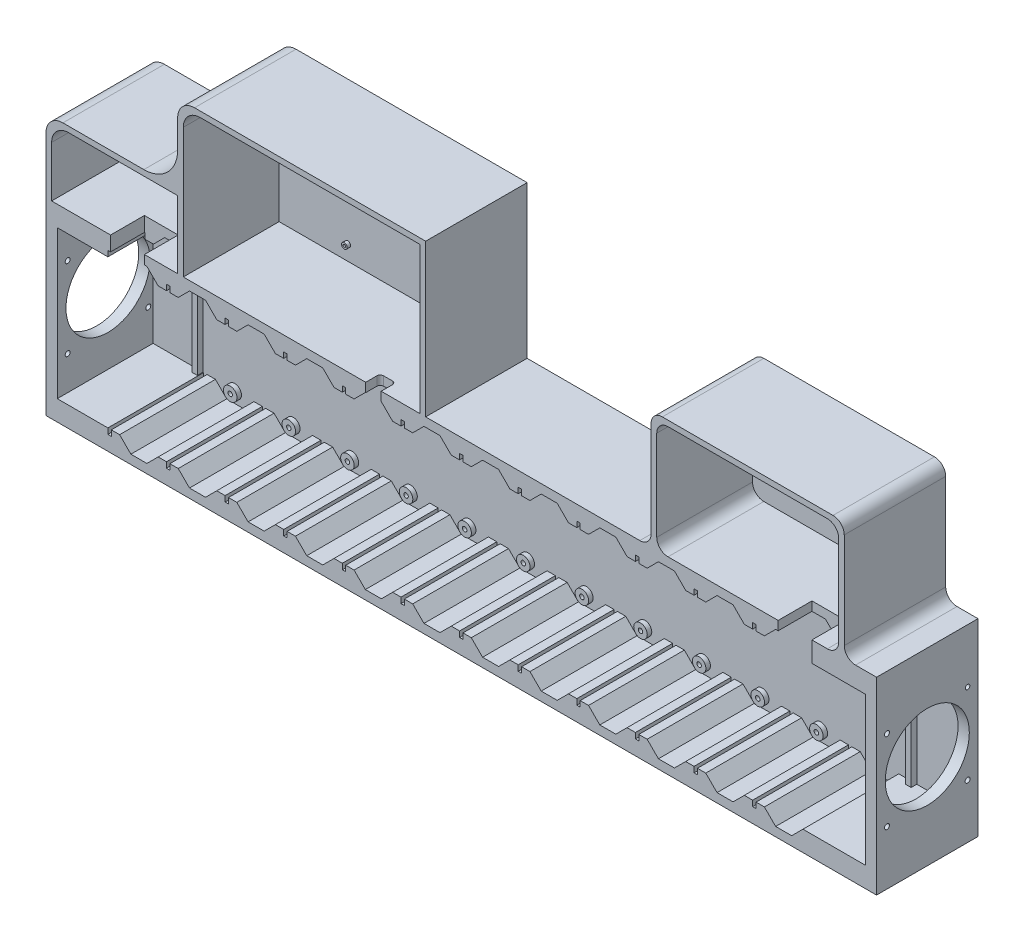
SolidWorks part; units mm, degrees
ref_plane "Front Plane" through (0, 0, 0) normal (0, 0, 1) x (1, 0, 0)
ref_plane "Top Plane" through (0, 0, 0) normal (0, 1, 0) x (1, 0, 0)
ref_plane "Right Plane" through (0, 0, 0) normal (1, 0, 0) x (0, 0, -1)
sketch "Szkic1" plane through (0, 0, 0) normal (0, 0, 1) x (1, 0, 0)
  line L0 (-48.95, 65) -> (-38.65, 65)
  line L1 (-38.65, 65) -> (-28.65, 75)
  line L2 (-28.65, 75) -> (-14.45, 75)
  line L3 (-14.45, 75) -> (-4.45, 65)
  line L4 (-4.45, 65) -> (13.35, 65)
  line L5 (13.35, 65) -> (23.35, 75)
  line L6 (23.35, 75) -> (37.55, 75)
  line L7 (37.55, 75) -> (47.55, 65)
  line L8 (-48.95, -66.4) -> (-38.65, -66.4)
  line L9 (-38.65, -66.4) -> (-28.65, -76.4)
  line L10 (-28.65, -76.4) -> (-14.45, -76.4)
  line L11 (-14.45, -76.4) -> (-4.45, -66.4)
  line L12 (-4.45, -66.4) -> (13.35, -66.4)
  line L13 (13.35, -66.4) -> (23.35, -76.4)
  line L14 (23.35, -76.4) -> (37.55, -76.4)
  line L15 (37.55, -76.4) -> (47.55, -66.4)
  line L16 (47.55, 65) -> (65.35, 65)
  line L17 (47.55, -66.4) -> (65.35, -66.4)
  line L18 (65.35, 65) -> (75.35, 75)
  line L19 (75.35, 75) -> (89.55, 75)
  line L20 (89.55, 75) -> (99.55, 65)
  line L21 (99.55, 65) -> (117.35, 65)
  line L22 (117.35, 65) -> (127.35, 75)
  line L23 (127.35, 75) -> (141.55, 75)
  line L24 (141.55, 75) -> (151.55, 65)
  line L25 (65.35, -66.4) -> (75.35, -76.4)
  line L26 (75.35, -76.4) -> (89.55, -76.4)
  line L27 (89.55, -76.4) -> (99.55, -66.4)
  line L28 (99.55, -66.4) -> (117.35, -66.4)
  line L29 (117.35, -66.4) -> (127.35, -76.4)
  line L30 (127.35, -76.4) -> (141.55, -76.4)
  line L31 (141.55, -76.4) -> (151.55, -66.4)
  line L32 (151.55, 65) -> (169.35, 65)
  line L33 (151.55, -66.4) -> (169.35, -66.4)
  line L34 (169.35, 65) -> (179.35, 75)
  line L35 (179.35, 75) -> (193.55, 75)
  line L36 (193.55, 75) -> (203.55, 65)
  line L37 (203.55, 65) -> (221.35, 65)
  line L38 (221.35, 65) -> (231.35, 75)
  line L39 (231.35, 75) -> (245.55, 75)
  line L40 (245.55, 75) -> (255.55, 65)
  line L41 (169.35, -66.4) -> (179.35, -76.4)
  line L42 (179.35, -76.4) -> (193.55, -76.4)
  line L43 (193.55, -76.4) -> (203.55, -66.4)
  line L44 (203.55, -66.4) -> (221.35, -66.4)
  line L45 (221.35, -66.4) -> (231.35, -76.4)
  line L46 (231.35, -76.4) -> (245.55, -76.4)
  line L47 (245.55, -76.4) -> (255.55, -66.4)
  line L48 (255.55, 65) -> (273.35, 65)
  line L49 (255.55, -66.4) -> (273.35, -66.4)
  line L50 (273.35, 65) -> (283.35, 75)
  line L51 (283.35, 75) -> (297.55, 75)
  line L52 (297.55, 75) -> (307.55, 65)
  line L53 (307.55, 65) -> (325.35, 65)
  line L54 (325.35, 65) -> (335.35, 75)
  line L55 (335.35, 75) -> (349.55, 75)
  line L56 (349.55, 75) -> (359.55, 65)
  line L57 (273.35, -66.4) -> (283.35, -76.4)
  line L58 (283.35, -76.4) -> (297.55, -76.4)
  line L59 (297.55, -76.4) -> (307.55, -66.4)
  line L60 (307.55, -66.4) -> (325.35, -66.4)
  line L61 (325.35, -66.4) -> (335.35, -76.4)
  line L62 (335.35, -76.4) -> (349.55, -76.4)
  line L63 (349.55, -76.4) -> (359.55, -66.4)
  line L64 (359.55, 65) -> (377.35, 65)
  line L65 (359.55, -66.4) -> (377.35, -66.4)
  line L66 (377.35, 65) -> (387.35, 75)
  line L67 (387.35, 75) -> (401.55, 75)
  line L68 (401.55, 75) -> (411.55, 65)
  line L69 (411.55, 65) -> (429.35, 65)
  line L70 (429.35, 65) -> (439.35, 75)
  line L71 (439.35, 75) -> (453.55, 75)
  line L72 (453.55, 75) -> (463.55, 65)
  line L73 (377.35, -66.4) -> (387.35, -76.4)
  line L74 (387.35, -76.4) -> (401.55, -76.4)
  line L75 (401.55, -76.4) -> (411.55, -66.4)
  line L76 (411.55, -66.4) -> (429.35, -66.4)
  line L77 (429.35, -66.4) -> (439.35, -76.4)
  line L78 (439.35, -76.4) -> (453.55, -76.4)
  line L79 (453.55, -76.4) -> (463.55, -66.4)
  line L80 (463.55, 65) -> (481.35, 65)
  line L81 (463.55, -66.4) -> (481.35, -66.4)
  line L82 (481.35, 65) -> (491.35, 75)
  line L83 (491.35, 75) -> (505.55, 75)
  line L84 (505.55, 75) -> (515.55, 65)
  line L85 (515.55, 65) -> (533.35, 65)
  line L86 (533.35, 65) -> (543.35, 75)
  line L87 (543.35, 75) -> (557.55, 75)
  line L88 (557.55, 75) -> (567.55, 65)
  line L89 (481.35, -66.4) -> (491.35, -76.4)
  line L90 (491.35, -76.4) -> (505.55, -76.4)
  line L91 (505.55, -76.4) -> (515.55, -66.4)
  line L92 (515.55, -66.4) -> (533.35, -66.4)
  line L93 (533.35, -66.4) -> (543.35, -76.4)
  line L94 (543.35, -76.4) -> (557.55, -76.4)
  line L95 (557.55, -76.4) -> (567.55, -66.4)
  line L96 (567.55, 65) -> (577.85, 65)
  line L97 (567.55, -66.4) -> (577.85, -66.4)
  line L100 (-48.95, 65) -> (-48.95, -66.4)
  line L101 (577.85, 65) -> (577.85, -66.4)
  line L103 (-103.95, 83) -> (632.85, 83)
  line L104 (-103.95, 83) -> (-103.95, -84.4)
  line L105 (-103.95, -84.4) -> (632.85, -84.4)
  line L106 (632.85, 83) -> (632.85, -84.4)
  circle A0 centre (-21.55, -67) radius 2
  circle A1 centre (30.45, -67) radius 2
  circle A2 centre (-21.55, 67) radius 2
  circle A3 centre (30.45, 67) radius 2
  circle A4 centre (82.45, -67) radius 2
  circle A5 centre (134.45, -67) radius 2
  circle A6 centre (82.45, 67) radius 2
  circle A7 centre (134.45, 67) radius 2
  circle A8 centre (186.45, -67) radius 2
  circle A9 centre (238.45, -67) radius 2
  circle A10 centre (186.45, 67) radius 2
  circle A11 centre (238.45, 67) radius 2
  circle A12 centre (290.45, -67) radius 2
  circle A13 centre (342.45, -67) radius 2
  circle A14 centre (290.45, 67) radius 2
  circle A15 centre (342.45, 67) radius 2
  circle A16 centre (394.45, -67) radius 2
  circle A17 centre (446.45, -67) radius 2
  circle A18 centre (394.45, 67) radius 2
  circle A19 centre (446.45, 67) radius 2
  circle A20 centre (498.45, -67) radius 2
  circle A21 centre (550.45, -67) radius 2
  circle A22 centre (498.45, 67) radius 2
  circle A23 centre (550.45, 67) radius 2
  circle A24 centre (-21.55, 67) radius 6
  circle A25 centre (30.45, 67) radius 6
  circle A26 centre (82.45, 67) radius 6
  circle A27 centre (134.45, 67) radius 6
  circle A28 centre (186.45, 67) radius 6
  circle A29 centre (238.45, 67) radius 6
  circle A30 centre (290.45, 67) radius 6
  circle A31 centre (342.45, 67) radius 6
  circle A32 centre (394.45, 67) radius 6
  circle A33 centre (446.45, 67) radius 6
  circle A34 centre (498.45, 67) radius 6
  circle A35 centre (550.45, 67) radius 6
  circle A36 centre (-21.55, -67) radius 6
  circle A37 centre (30.45, -67) radius 2
  circle A38 centre (30.45, -67) radius 6
  circle A39 centre (82.45, -67) radius 6
  circle A40 centre (134.45, -67) radius 6
  circle A41 centre (186.45, -67) radius 6
  circle A42 centre (238.45, -67) radius 6
  circle A43 centre (290.45, -67) radius 6
  circle A44 centre (342.45, -67) radius 6
  circle A45 centre (394.45, -67) radius 6
  circle A46 centre (446.45, -67) radius 6
  circle A47 centre (498.45, -67) radius 6
  circle A48 centre (550.45, -67) radius 6
  dimension "D10" = 4
  dimension "D11" = 4
  dimension "D13" = 4
  dimension "D14" = 4
  dimension "D1" = 104
  dimension "D2" = 17.8
  dimension "D3" = 17.8
  dimension "D4" = 17.8
  dimension "D6" = 10.3
  dimension "D7" = 10.3
  dimension "D8" = 10.3
  dimension "D9" = 10.3
  dimension "D16" = 55
  dimension "D17" = 8
  dimension "D18" = 8
  dimension "D19" = 55
  dimension "D12" = 6
  dimension "D15" = 6
extrude "Dodanie-wyciągnięcie1" add sketch "Szkic1" along normal blind 4 contours A24 A2 | A25 A3 | A26 A6 | A27 | A28 | A29 | A30 | A31 | A32 | A33 | A34 | A35 | A48 | A47 | A46 | A45 | A44 | A43 | A42 | A41 | A40 | A39 | A38 | A36 region at (-27.3803, 67, 0) region at (24.6197, 67, 0) region at (76.6197, 67, 0)
extrude "Dodanie-wyciągnięcie2" add sketch "Szkic1<3>" against normal blind 5 contours L101 L96 L88 L87 L86 L85 L84 L83 L82 L80 L72 L71 L70 L69 L68 L67 L66 L64 L56 L55 L54 L53 L52 L51 L50 L48 L40 L39 L38 L37 L36 L35 L34 L32 L24 L23 L22 L21 L20 L19 L18 L16 L7 L6 L5 L4 L3 L2 L1 L0 L100 region at (264.45, -0.7222, 0)
sketch "Szkic1<3>" plane through (0, 0, 0) normal (0, 0, 1) x (1, 0, 0) same geometry as "Szkic1"
extrude "Dodanie-wyciągnięcie3" add sketch "Szkic1<4>" along normal blind 90 from offset 5 contours L106 L103 L104 L105 L96 L101 L97 L95 L94 L93 L92 L91 L90 L89 L81 L79 L78 L77 L76 L75 L74 L73 L65 L63 L62 L61 L60 L59 L58 L57 L49 L47 L46 L45 L44 L43 L42 L41 L33 L31 L30 L29 L28 L27 L26 L25 L17 L15 L14 L13 region at (264.45, 75.4442, 0) offset against normal yes
sketch "Szkic1<4>" plane through (0, 0, 0) normal (0, 0, 1) x (1, 0, 0) same geometry as "Szkic1"
sketch "Szkic2" plane through (0, 0, -5) normal (0, 0, -1) x (-1, 0, 0)
  line L1 (-632.85, 83) -> (103.95, 83)
  line L2 (-632.85, 83) -> (-632.85, -84.4)
  line L3 (-632.85, -84.4) -> (103.95, -84.4)
  line L4 (103.95, 83) -> (103.95, -84.4)
extrude "Dodanie-wyciągnięcie4" add sketch "Szkic2" against normal blind 5
sketch "Szkic3" plane through (0, 0, 4) normal (0, 0, 1) x (1, 0, 0)
  circle A2 centre (550.45, -67) radius 2
  circle A3 centre (550.45, 67) radius 2
  circle A4 centre (498.45, 67) radius 2
  circle A5 centre (498.45, -67) radius 2
  circle A6 centre (446.45, 67) radius 2
  circle A7 centre (446.45, -67) radius 2
  circle A8 centre (394.45, 67) radius 2
  circle A9 centre (394.45, -67) radius 2
  circle A10 centre (342.45, 67) radius 2
  circle A11 centre (342.45, -67) radius 2
  circle A12 centre (290.45, 67) radius 2
  circle A13 centre (290.45, -67) radius 2
  circle A14 centre (238.45, 67) radius 2
  circle A15 centre (238.45, -67) radius 2
  circle A16 centre (186.45, 67) radius 2
  circle A17 centre (186.45, -67) radius 2
  circle A18 centre (134.45, 67) radius 2
  circle A19 centre (134.45, -67) radius 2
  circle A20 centre (82.45, 67) radius 2
  circle A21 centre (82.45, -67) radius 2
  circle A22 centre (30.45, 67) radius 2
  circle A23 centre (30.45, -67) radius 2
  circle A24 centre (-21.55, 67) radius 2
  circle A25 centre (-21.55, -67) radius 2
  dimension "D1" = 4
  dimension "D2" = 4
  dimension "D3" = 12
extrude "Wytnij-wyciągnięcie1" cut sketch "Szkic3" against normal blind 4
sketch "Szkic4" plane through (0, 0, 85) normal (0, 0, 1) x (1, 0, 0)
  line L0 (-48.95, -66.4) -> (-38.65, -66.4) construction
  line L1 (-48.95, 65) -> (-93.95, 65)
  line L2 (-48.95, 65) -> (-48.95, -66.4)
  line L3 (-48.95, -66.4) -> (-93.95, -66.4)
  line L4 (-93.95, 65) -> (-93.95, -66.4)
  line L5 (-103.95, 83) -> (-103.95, -84.4) construction
  line L6 (632.85, 83) -> (632.85, -84.4) construction
  line L7 (577.85, 65) -> (622.85, 65)
  line L8 (577.85, 65) -> (577.85, -66.4)
  line L9 (577.85, -66.4) -> (622.85, -66.4)
  line L10 (622.85, 65) -> (622.85, -66.4)
  dimension "D1" = 0
  dimension "D2" = 10
  dimension "D3" = 10
extrude "Wytnij-wyciągnięcie2" cut sketch "Szkic4" against normal blind 85 contours L1 L4 L3 L2 | L10 L7 L8 L9 | L10 L7 L8 L9 | L1 L4 L3 L2 region at (-71.45, -0.7, 85) region at (600.35, -0.7, 85)
sketch "Szkic5" plane through (0, 0, 0) normal (0, 0, 1) x (1, 0, 0)
  line L1 (-49.65, 65) -> (-54.65, 65)
  line L2 (-49.65, 65) -> (-49.65, -66.4)
  line L3 (-49.65, -66.4) -> (-54.65, -66.4)
  line L4 (-54.65, 65) -> (-54.65, -66.4)
  line L7 (578.55, 65) -> (583.55, 65)
  line L8 (578.55, 65) -> (578.55, -66.4)
  line L9 (578.55, -66.4) -> (583.55, -66.4)
  line L10 (583.55, 65) -> (583.55, -66.4)
  dimension "D1" = 11
  dimension "D2" = 5
  dimension "D3" = 11
  dimension "D4" = 5
  dimension "D5" = 5
  dimension "D6" = 5
extrude "Dodanie-wyciągnięcie5" add sketch "Szkic5" along normal blind 5
sketch "Szkic7" plane through (-103.95, 0, 0) normal (-1, 0, 0) x (0, 0, 1)
  line L0 (-5, -84.4) -> (-5, 83) construction
  line L1 (-5, 63) -> (85, 63)
  line L2 (-5, 63) -> (-5, -64.4)
  line L3 (-5, -64.4) -> (85, -64.4)
  line L4 (85, 63) -> (85, -64.4)
  line L5 (85, 83) -> (85, -84.4) construction
  line L6 (85, 83) -> (-5, 83) construction
  line L7 (85, -84.4) -> (-5, -84.4) construction
  circle A1 centre (4.25, 35.05) radius 2
  circle A2 centre (75.75, 35.05) radius 2.2
  circle A3 centre (4.25, -36.45) radius 2.2
  circle A4 centre (75.75, -36.45) radius 2.2
  circle A5 centre (40, -0.7) radius 37.2941
  dimension "D3" = 50.5581
  dimension "D1" = 20
  dimension "D2" = 20
  dimension "D4" = 50.5581
  dimension "D5" = 50.5581
  dimension "D6" = 167.4
  dimension "D7" = 50.5581
  dimension "D8" = 45
  dimension "D9" = 83.7
extrude "Wytnij-wyciągnięcie5" cut sketch "Szkic7" against normal blind 15 contours A1 | A5 | A2 | A4 | A3 region at (-103.95, 35.05, 4.25) region at (-103.95, -0.7, 40)
extrude "Wytnij-wyciągnięcie7" cut sketch "Szkic7<3>" against normal blind 5000 from offset 700 contours A5 | A2 | A1 | A4 | A3 region at (-103.95, -0.7, 40) offset against normal yes
sketch "Szkic7<3>" plane through (-103.95, 0, 0) normal (-1, 0, 0) x (0, 0, 1) same geometry as "Szkic7"
sketch "Szkic8" plane through (0, 83, 0) normal (0, 1, 0) x (1, 0, 0)
  line L0 (-103.95, -85) -> (632.85, -85) construction
  line L1 (545.55, -85) -> (575.55, -85)
  line L2 (545.55, -85) -> (545.55, -55)
  line L3 (545.55, -55) -> (575.55, -55)
  line L4 (575.55, -85) -> (575.55, -55)
  line L6 (-103.95, 5) -> (632.85, 5) construction
  line L7 (264.45, -85) -> (264.45, 5)
  line L8 (-16.65, -85) -> (-46.65, -85)
  line L9 (-46.65, -85) -> (-46.65, -55)
  line L10 (-16.65, -55) -> (-46.65, -55)
  line L11 (-16.65, -85) -> (-16.65, -55)
  line M8 (-103.95, -85) -> (632.85, -85)
  dimension "D1" = 12
  dimension "D2" = 30
  dimension "D3" = 60
extrude "Wytnij-wyciągnięcie8" cut sketch "Szkic8" against normal blind 40 contours L11 L10 L9 M8 | L4 L3 L2 M8 region at (560.55, 83, 70) region at (-31.65, 83, 70)
sketch "Szkic9" plane through (0, 83, 0) normal (0, 1, 0) x (1, 0, 0)
  line L0 (604.2, -85) -> (604.2, 5)
  line L1 (575.55, -85) -> (632.85, -85) construction
  line L2 (-103.95, 5) -> (632.85, 5) construction
  line L3 (604.2, 5) -> (432.85, 5)
  line L4 (432.85, 5) -> (432.85, -85)
  line L5 (-16.65, -85) -> (545.55, -85) construction
  line L6 (432.85, -85) -> (437.85, -85)
  line L7 (437.85, -85) -> (437.85, 0)
  line L8 (437.85, 0) -> (599.2, 0)
  line L9 (599.2, 0) -> (599.2, -85)
  line L10 (599.2, -85) -> (604.2, -85)
  line L12 (632.85, -85) -> (632.85, 5) construction
  dimension "D1" = 200
  dimension "D2" = 5
  dimension "D3" = 5
  dimension "D4" = 5
extrude "Dodanie-wyciągnięcie6" add sketch "Szkic9" along normal blind 100
sketch "Szkic10" plane through (0, 0, 0) normal (0, 0, 1) x (1, 0, 0)
  line L1 (544.2, 110.9641) -> (544.2, 161.1291)
  line L3 (488.32, 115.7757) -> (488.32, 161.1291)
  line L5 (526.7866, 104.8109) -> (544.2, 104.8109)
  line L6 (544.2, 104.8109) -> (544.2, 110.9641)
  line L7 (488.32, 115.7757) -> (488.32, 105.2491)
  line L8 (488.32, 105.2491) -> (501.1716, 105.2491)
  line L9 (604.2, 183) -> (604.2, 83) construction
  line L11 (526.7866, 104.8109) -> (501.1716, 105.2491)
  line L12 (488.32, 161.1291) -> (488.32, 105.2491) construction
  line L13 (544.2, 161.1291) -> (488.32, 161.1291)
  circle A0 centre (493.9743, 155.4141) radius 2.6543
  circle A1 centre (538.4243, 110.9641) radius 2.6543
  point P14 (495.9509, 133.06)
  dimension "D5" = 5.715
  dimension "D1" = 60
  dimension "D2" = 55.88
  dimension "D3" = 45.3534
  dimension "D4" = 10.5266
  dimension "D6" = 6.1532
  dimension "D7" = 5.7757
  dimension "D8" = 5.6543
sketch "Szkic11" plane through (0, 183, 0) normal (0, 1, 0) x (1, 0, 0)
  line L1 (432.85, 5) -> (604.2, 5)
  line L2 (432.85, 5) -> (432.85, -85)
  line L3 (432.85, -85) -> (604.2, -85)
  line L4 (604.2, 5) -> (604.2, -85)
extrude "Dodanie-wyciągnięcie7" add sketch "Szkic11" along normal blind 5
extrude "Dodanie-wyciągnięcie8" add sketch "Szkic10" along normal blind 5 contours L11 L5 L6 L1 L3 L7 L8 A1 A0 region at (516.3119, 133.0686, 0)
fillet "Zaokrąglenie1" radius 10 8 edges at (599.2, 183, 42.5) (604.2, 83, 40) (432.85, 83, 40) (432.85, 188, 40) (604.2, 188, 40) (437.85, 183, 42.5) (437.85, 83, 42.5) (599.2, 83, 42.5)
sketch "Szkic12" plane through (0, 83, 0) normal (0, 1, 0) x (1, 0, 0)
  line L0 (12.85, -85) -> (12.85, 5)
  line L1 (-16.65, -85) -> (422.85, -85) construction
  line L2 (-103.95, 5) -> (422.85, 5) construction
  line L3 (12.85, 5) -> (232.85, 5)
  line L4 (232.85, 5) -> (232.85, -85)
  line L5 (232.85, -85) -> (227.85, -85)
  line L6 (227.85, -85) -> (227.85, 0)
  line L7 (227.85, 0) -> (17.85, 0)
  line L8 (17.85, 0) -> (17.85, -85)
  line L9 (17.85, -85) -> (12.85, -85)
  line L10 (632.85, -85) -> (632.85, 5) construction
  line L11 (-103.95, -85) -> (-103.95, 5)
  line L12 (-103.95, 5) -> (12.85, 5)
  line L13 (-98.95, 0) -> (-98.95, -85)
  line L14 (-98.95, -85) -> (-103.95, -85)
  line L15 (-98.95, 0) -> (12.85, 0)
  line M6 (-16.65, -85) -> (422.85, -85)
  line M8 (422.85, 5) -> (-103.95, 5)
  line M9 (-103.95, 5) -> (-103.95, -85)
  line M10 (-103.95, -85) -> (-46.65, -85)
  dimension "D1" = 5
  dimension "D2" = 5
  dimension "D3" = 5
  dimension "D4" = 400
  dimension "D5" = 220
  dimension "D6" = 5
extrude "Dodanie-wyciągnięcie9" add sketch "Szkic12" along normal blind 130 contours L8 L7 L6 L4 L0 M6 M8 region at (15.227, 83, 42.5)
sketch "Szkic13" plane through (0, 0, 0) normal (0, 0, 1) x (1, 0, 0)
  circle A0 centre (220.758, 96.3454) radius 1.1
  circle A1 centre (220.758, 145.8454) radius 1.1
  circle A2 centre (78.758, 164.3454) radius 1.1
  circle A3 centre (78.758, 96.3454) radius 1.1
  circle A4 centre (220.758, 96.3454) radius 2.5
  circle A5 centre (220.758, 145.8454) radius 2.5
  circle A6 centre (78.758, 164.3454) radius 2.5
  circle A7 centre (78.758, 96.3454) radius 2.5
  point P2 (220.758, 145.8454)
  point P5 (78.758, 164.3454)
  point P8 (78.758, 96.3454)
  dimension "D1" = 5
  dimension "D2" = 5
  dimension "D3" = 5
  dimension "D4" = 5
extrude "Dodanie-wyciągnięcie10" add sketch "Szkic13" along normal blind 3
sketch "Szkic14" plane through (0, 213, 0) normal (0, 1, 0) x (1, 0, 0)
  line L5 (12.85, 5) -> (232.85, 5)
  line L6 (12.85, 5) -> (12.85, -85)
  line L7 (12.85, -85) -> (232.85, -85)
  line L8 (232.85, 5) -> (232.85, -85)
sketch "Szkic15" plane through (0, 0, 85) normal (0, 0, 1) x (1, 0, 0)
  line L0 (515.55, 65) -> (533.35, 65) construction
  line L1 (522.95, 70) -> (525.95, 70)
  line L2 (522.95, 70) -> (522.95, 65)
  line L3 (522.95, 65) -> (525.95, 65)
  line L4 (525.95, 70) -> (525.95, 65)
  line L6 (470.95, 70) -> (473.95, 70)
  line L7 (470.95, 70) -> (470.95, 65)
  line L8 (473.95, 70) -> (473.95, 65)
  line L9 (470.95, 65) -> (473.95, 65)
  line L10 (418.95, 70) -> (421.95, 70)
  line L11 (418.95, 70) -> (418.95, 65)
  line L12 (421.95, 70) -> (421.95, 65)
  line L13 (418.95, 65) -> (421.95, 65)
  line L14 (366.95, 70) -> (369.95, 70)
  line L15 (366.95, 70) -> (366.95, 65)
  line L16 (369.95, 70) -> (369.95, 65)
  line L17 (366.95, 65) -> (369.95, 65)
  line L18 (314.95, 70) -> (317.95, 70)
  line L19 (314.95, 70) -> (314.95, 65)
  line L20 (317.95, 70) -> (317.95, 65)
  line L21 (314.95, 65) -> (317.95, 65)
  line L22 (262.95, 70) -> (265.95, 70)
  line L23 (262.95, 70) -> (262.95, 65)
  line L24 (265.95, 70) -> (265.95, 65)
  line L25 (262.95, 65) -> (265.95, 65)
  line L26 (210.95, 70) -> (213.95, 70)
  line L27 (210.95, 70) -> (210.95, 65)
  line L28 (213.95, 70) -> (213.95, 65)
  line L29 (210.95, 65) -> (213.95, 65)
  line L30 (158.95, 70) -> (161.95, 70)
  line L31 (158.95, 70) -> (158.95, 65)
  line L32 (161.95, 70) -> (161.95, 65)
  line L33 (158.95, 65) -> (161.95, 65)
  line L34 (106.95, 70) -> (109.95, 70)
  line L35 (106.95, 70) -> (106.95, 65)
  line L36 (109.95, 70) -> (109.95, 65)
  line L37 (106.95, 65) -> (109.95, 65)
  line L38 (54.95, 70) -> (57.95, 70)
  line L39 (54.95, 70) -> (54.95, 65)
  line L40 (57.95, 70) -> (57.95, 65)
  line L41 (54.95, 65) -> (57.95, 65)
  line L42 (2.95, 70) -> (5.95, 70)
  line L43 (2.95, 70) -> (2.95, 65)
  line L44 (5.95, 70) -> (5.95, 65)
  line L45 (2.95, 65) -> (5.95, 65)
  line L46 (-49.05, 70) -> (-46.05, 70)
  line L47 (-49.05, 70) -> (-49.05, 65)
  line L48 (-46.05, 70) -> (-46.05, 65)
  line L49 (-49.05, 65) -> (-46.05, 65)
  line L52 (-49.05, -66.4) -> (-46.05, -66.4)
  line L53 (-46.05, -71.4) -> (-46.05, -66.4)
  line L54 (-49.05, -71.4) -> (-49.05, -66.4)
  line L55 (-49.05, -71.4) -> (-46.05, -71.4)
  line L56 (2.95, -66.4) -> (5.95, -66.4)
  line L57 (5.95, -71.4) -> (5.95, -66.4)
  line L58 (2.95, -71.4) -> (2.95, -66.4)
  line L59 (2.95, -71.4) -> (5.95, -71.4)
  line L60 (54.95, -66.4) -> (57.95, -66.4)
  line L61 (57.95, -71.4) -> (57.95, -66.4)
  line L62 (54.95, -71.4) -> (54.95, -66.4)
  line L63 (54.95, -71.4) -> (57.95, -71.4)
  line L64 (106.95, -66.4) -> (109.95, -66.4)
  line L65 (109.95, -71.4) -> (109.95, -66.4)
  line L66 (106.95, -71.4) -> (106.95, -66.4)
  line L67 (106.95, -71.4) -> (109.95, -71.4)
  line L68 (158.95, -66.4) -> (161.95, -66.4)
  line L69 (161.95, -71.4) -> (161.95, -66.4)
  line L70 (158.95, -71.4) -> (158.95, -66.4)
  line L71 (158.95, -71.4) -> (161.95, -71.4)
  line L72 (210.95, -66.4) -> (213.95, -66.4)
  line L73 (213.95, -71.4) -> (213.95, -66.4)
  line L74 (210.95, -71.4) -> (210.95, -66.4)
  line L75 (210.95, -71.4) -> (213.95, -71.4)
  line L76 (262.95, -66.4) -> (265.95, -66.4)
  line L77 (265.95, -71.4) -> (265.95, -66.4)
  line L78 (262.95, -71.4) -> (262.95, -66.4)
  line L79 (262.95, -71.4) -> (265.95, -71.4)
  line L80 (314.95, -66.4) -> (317.95, -66.4)
  line L81 (317.95, -71.4) -> (317.95, -66.4)
  line L82 (314.95, -71.4) -> (314.95, -66.4)
  line L83 (314.95, -71.4) -> (317.95, -71.4)
  line L84 (366.95, -66.4) -> (369.95, -66.4)
  line L85 (369.95, -71.4) -> (369.95, -66.4)
  line L86 (366.95, -71.4) -> (366.95, -66.4)
  line L87 (366.95, -71.4) -> (369.95, -71.4)
  line L88 (418.95, -66.4) -> (421.95, -66.4)
  line L89 (421.95, -71.4) -> (421.95, -66.4)
  line L90 (418.95, -71.4) -> (418.95, -66.4)
  line L91 (418.95, -71.4) -> (421.95, -71.4)
  line L92 (470.95, -66.4) -> (473.95, -66.4)
  line L93 (473.95, -71.4) -> (473.95, -66.4)
  line L94 (470.95, -71.4) -> (470.95, -66.4)
  line L95 (470.95, -71.4) -> (473.95, -71.4)
  line L96 (525.95, -71.4) -> (525.95, -66.4)
  line L97 (522.95, -66.4) -> (525.95, -66.4)
  line L98 (522.95, -71.4) -> (522.95, -66.4)
  line L99 (522.95, -71.4) -> (525.95, -71.4)
  dimension "D1" = 3
  dimension "D2" = 7.4
  dimension "D3" = 5
  dimension "D4" = 12
extrude "Wytnij-wyciągnięcie9" cut sketch "Szkic15" against normal blind 85
sketch "Szkic17" plane through (0, 75, 0) normal (0, -1, 0) x (1, 0, 0)
  line L0 (-93.95, 85) -> (622.85, 85) construction
  line L1 (179.6342, 85) -> (193.4063, 85)
  line L2 (179.6342, 85) -> (179.6342, 72.0826)
  line L3 (179.6342, 72.0826) -> (193.4063, 72.0826)
  line L4 (193.4063, 85) -> (193.4063, 72.0826)
extrude "Wytnij-wyciągnięcie11" cut sketch "Szkic17" against normal blind 10
fillet "Zaokrąglenie4" radius 3 2 edges at (179.6342, 79, 72.0826) (193.4063, 79, 72.0826)
extrude "Dodanie-wyciągnięcie12" add sketch "Szkic12<3>" along normal blind 60 contours L13 L15 L0 M8 M9 M10 region at (-43.05, 83, -1.4745)
sketch "Szkic12<3>" plane through (0, 83, 0) normal (0, 1, 0) x (1, 0, 0) same geometry as "Szkic12"
sketch "Szkic19" plane through (0, 143, 0) normal (0, 1, 0) x (1, 0, 0)
  line L1 (-103.95, 5) -> (12.85, 5)
  line L2 (-103.95, 5) -> (-103.95, -85)
  line L3 (-103.95, -85) -> (12.85, -85)
  line L4 (12.85, 5) -> (12.85, -85)
extrude "Dodanie-wyciągnięcie14" add sketch "Szkic19" along normal blind 5
fillet "Zaokrąglenie5" radius 15 2 edges at (-98.95, 143, 42.5) (-103.95, 148, 40)
fillet "Zaokrąglenie6" radius 30 1 edges at (12.85, 148, 40)
sketch "Szkic20" plane through (0, 213, 0) normal (0, 1, 0) x (1, 0, 0)
  line L1 (12.85, 5) -> (232.85, 5)
  line L2 (12.85, 5) -> (12.85, -85)
  line L3 (12.85, -85) -> (232.85, -85)
  line L4 (232.85, 5) -> (232.85, -85)
extrude "Dodanie-wyciągnięcie15" add sketch "Szkic20" along normal blind 5
fillet "Zaokrąglenie8" radius 15 2 edges at (17.85, 213, 42.5) (12.85, 218, 40)
